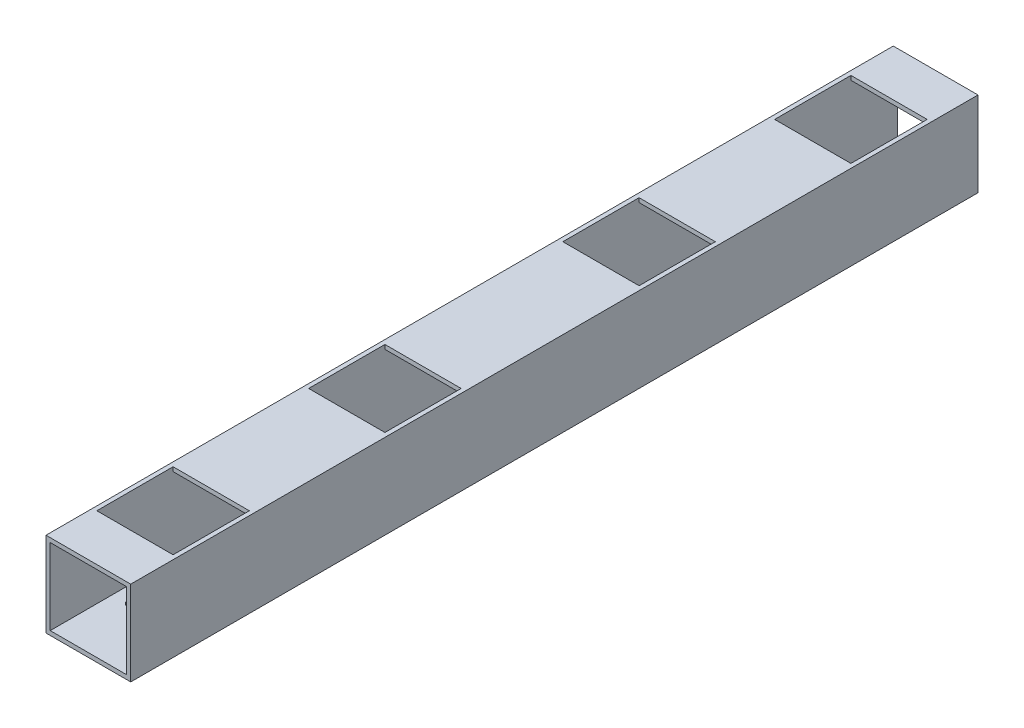
SolidWorks part; units mm, degrees
material "6061-T6 (SS)"
ref_plane "前视基准面" through (0, 0, 0) normal (0, 0, 1) x (1, 0, 0)
ref_plane "上视基准面" through (0, 0, 0) normal (0, 1, 0) x (1, 0, 0)
ref_plane "右视基准面" through (0, 0, 0) normal (1, 0, 0) x (0, 0, -1)
sketch "草图1" plane through (0, 0, 0) normal (0, 0, 1) x (1, 0, 0)
  line L1 (-10, 10) -> (10, 10)
  line L2 (-10, 10) -> (-10, -10)
  line L3 (-10, -10) -> (10, -10)
  line L4 (10, 10) -> (10, -10)
  line L5 (-10, 10) -> (10, -10) construction
  line L6 (-10, -10) -> (10, 10) construction
  line L7 (-9, 9) -> (9, 9)
  line L8 (-9, 9) -> (-9, -9)
  line L9 (-9, -9) -> (9, -9)
  line L10 (9, 9) -> (9, -9)
  line L11 (-9, 9) -> (9, -9) construction
  line L12 (-9, -9) -> (9, 9) construction
  point P0 (0, 0)
  point P6 (0, 0)
  dimension "D1" = 20
  dimension "D2" = 20
  dimension "D3" = 18
  dimension "D4" = 18
extrude "凸台-拉伸1" add sketch "草图1" along normal blind 200
sketch "草图3" plane through (0, 10, 0) normal (0, 1, 0) x (1, 0, 0)
  line L0 (-10, -140) -> (10, -120) construction
  line L5 (-10, -190) -> (10, -170) construction
  line L6 (-10, -170) -> (10, -170) construction
  line L7 (-10, -120) -> (10, -120) construction
  line L8 (-10, -120) -> (-10, -80) construction
  line L9 (-10, -80) -> (10, -80) construction
  line L10 (10, -120) -> (10, -80) construction
  line L11 (-10, -120) -> (10, -80) construction
  line L12 (-10, -80) -> (10, -120) construction
  line L13 (-10, -140) -> (10, -140) construction
  line L14 (-10, -140) -> (-10, -60) construction
  line L15 (-10, -60) -> (10, -60) construction
  line L16 (10, -140) -> (10, -60) construction
  line L17 (-10, -140) -> (10, -60) construction
  line L18 (-10, -60) -> (10, -140) construction
  line L19 (-10, -120) -> (10, -140) construction
  line L20 (4.5, -134.5) -> (13.5, -134.5) construction
  line L21 (-4.5, -134.5) -> (4.5, -134.5) construction
  line L22 (-4.5, -134.5) -> (-4.5, -125.5) construction
  line L23 (-4.5, -125.5) -> (4.5, -125.5) construction
  line L24 (4.5, -134.5) -> (4.5, -125.5) construction
  line L25 (-4.5, -134.5) -> (4.5, -125.5) construction
  line L26 (-4.5, -125.5) -> (4.5, -134.5) construction
  line L27 (4.5, -134.5) -> (4.5, -125.5) construction
  line L28 (4.5, -125.5) -> (13.5, -125.5) construction
  line L29 (4.5, -125.5) -> (4.5, -116.5) construction
  line L30 (-4.5, -125.5) -> (4.5, -125.5) construction
  line L31 (-4.5, -125.5) -> (-4.5, -116.5) construction
  line L32 (0, -100) -> (-32.7299, -100) construction
  line L33 (-10, -190) -> (10, -190) construction
  line L34 (-10, -170) -> (10, -190) construction
  line L35 (4.5, -184.5) -> (13.5, -184.5) construction
  line L36 (-4.5, -184.5) -> (4.5, -184.5) construction
  line L37 (-4.5, -184.5) -> (-4.5, -175.5) construction
  line L38 (-4.5, -175.5) -> (4.5, -175.5) construction
  line L39 (4.5, -184.5) -> (4.5, -175.5) construction
  line L40 (-4.5, -184.5) -> (4.5, -175.5) construction
  line L41 (-4.5, -175.5) -> (4.5, -184.5) construction
  line L42 (4.5, -184.5) -> (4.5, -175.5) construction
  line L43 (4.5, -175.5) -> (13.5, -175.5) construction
  line L44 (4.5, -175.5) -> (4.5, -166.5) construction
  line L45 (-4.5, -175.5) -> (4.5, -175.5) construction
  line L46 (-4.5, -175.5) -> (-4.5, -166.5) construction
  line L47 (-4.5, -24.5) -> (-4.5, -33.5) construction
  line L48 (-4.5, -24.5) -> (4.5, -24.5) construction
  line L49 (4.5, -24.5) -> (4.5, -33.5) construction
  line L50 (4.5, -24.5) -> (13.5, -24.5) construction
  line L51 (4.5, -15.5) -> (4.5, -24.5) construction
  line L52 (-4.5, -24.5) -> (4.5, -15.5) construction
  line L53 (-4.5, -15.5) -> (4.5, -24.5) construction
  line L54 (4.5, -15.5) -> (4.5, -24.5) construction
  line L55 (-4.5, -24.5) -> (4.5, -24.5) construction
  line L56 (-4.5, -15.5) -> (-4.5, -24.5) construction
  line L57 (-4.5, -15.5) -> (4.5, -15.5) construction
  line L58 (4.5, -15.5) -> (13.5, -15.5) construction
  line L59 (-10, -30) -> (10, -10) construction
  line L60 (-10, -10) -> (10, -10) construction
  line L61 (-10, -30) -> (10, -30) construction
  line L62 (-10, -10) -> (10, -30) construction
  circle A0 centre (-4.5, -134.5) radius 1.6
  circle A1 centre (4.5, -134.5) radius 1.6
  circle A2 centre (4.5, -125.5) radius 1.6
  circle A3 centre (-4.5, -125.5) radius 1.6
  circle A4 centre (4.5, -65.5) radius 1.6
  circle A5 centre (4.5, -74.5) radius 1.6
  circle A6 centre (-4.5, -74.5) radius 1.6
  circle A7 centre (-4.5, -65.5) radius 1.6
  circle A16 centre (-4.5, -184.5) radius 1.6
  circle A17 centre (4.5, -184.5) radius 1.6
  circle A18 centre (4.5, -175.5) radius 1.6
  circle A19 centre (-4.5, -175.5) radius 1.6
  circle A20 centre (-4.5, -24.5) radius 1.6
  circle A21 centre (4.5, -24.5) radius 1.6
  circle A22 centre (4.5, -15.5) radius 1.6
  circle A23 centre (-4.5, -15.5) radius 1.6
  point P4 (0, -100)
  point P7 (0, -100)
  point P12 (0, -100)
  point P17 (0, -130)
  point P46 (0, -180)
  point P79 (0, -20)
  dimension "D5" = 2
  dimension "D1" = 40
  dimension "D2" = 80
  dimension "D3" = 9
  dimension "D4" = 9
  dimension "D6" = 2
  dimension "D7" = 2
extrude "切除-拉伸1" cut sketch "草图3" against normal through all
sketch "草图4" plane through (0, 10, 0) normal (0, 1, 0) x (1, 0, 0)
  line L0 (-9, -121) -> (-9, -139)
  line L1 (-4.5, -65.5) -> (4.5, -65.5) construction
  line L2 (-4.5, -65.5) -> (-4.5, -74.5) construction
  line L3 (-4.5, -74.5) -> (4.5, -74.5) construction
  line L4 (4.5, -65.5) -> (4.5, -74.5) construction
  line L5 (-4.5, -65.5) -> (4.5, -74.5) construction
  line L6 (-4.5, -74.5) -> (4.5, -65.5) construction
  line L7 (-9, -61) -> (9, -61)
  line L8 (-9, -61) -> (-9, -79)
  line L9 (-9, -79) -> (9, -79)
  line L10 (9, -61) -> (9, -79)
  line L11 (-9, -61) -> (9, -79) construction
  line L12 (-9, -79) -> (9, -61) construction
  line L13 (-9, -121) -> (9, -121)
  line L14 (9, -121) -> (9, -139)
  line L15 (-9, -139) -> (9, -139)
  line L24 (-9, -11) -> (9, -11)
  line L25 (-9, -11) -> (-9, -29)
  line L26 (-9, -29) -> (9, -29)
  line L27 (9, -11) -> (9, -29)
  line L28 (-4.5, -15.5) -> (4.5, -15.5) construction
  line L29 (-4.5, -15.5) -> (-4.5, -24.5) construction
  line L30 (-4.5, -24.5) -> (4.5, -24.5) construction
  line L31 (4.5, -15.5) -> (4.5, -24.5) construction
  line L32 (-4.5, -15.5) -> (4.5, -24.5) construction
  line L33 (-4.5, -24.5) -> (4.5, -15.5) construction
  line L34 (-9, -11) -> (9, -29) construction
  line L35 (-9, -29) -> (9, -11) construction
  line L36 (-9, -171) -> (-9, -189)
  line L37 (-9, -171) -> (9, -171)
  line L38 (9, -171) -> (9, -189)
  line L39 (-9, -189) -> (9, -189)
  point P5 (0, -70)
  point P6 (0, -70)
  point P26 (0, -20)
  point P27 (0, -20)
  dimension "D1" = 18
  dimension "D2" = 18
  dimension "D3" = 2
  dimension "D5" = 2
  dimension "D4" = 2
extrude "切除-拉伸2" cut sketch "草图4" against normal up to next
